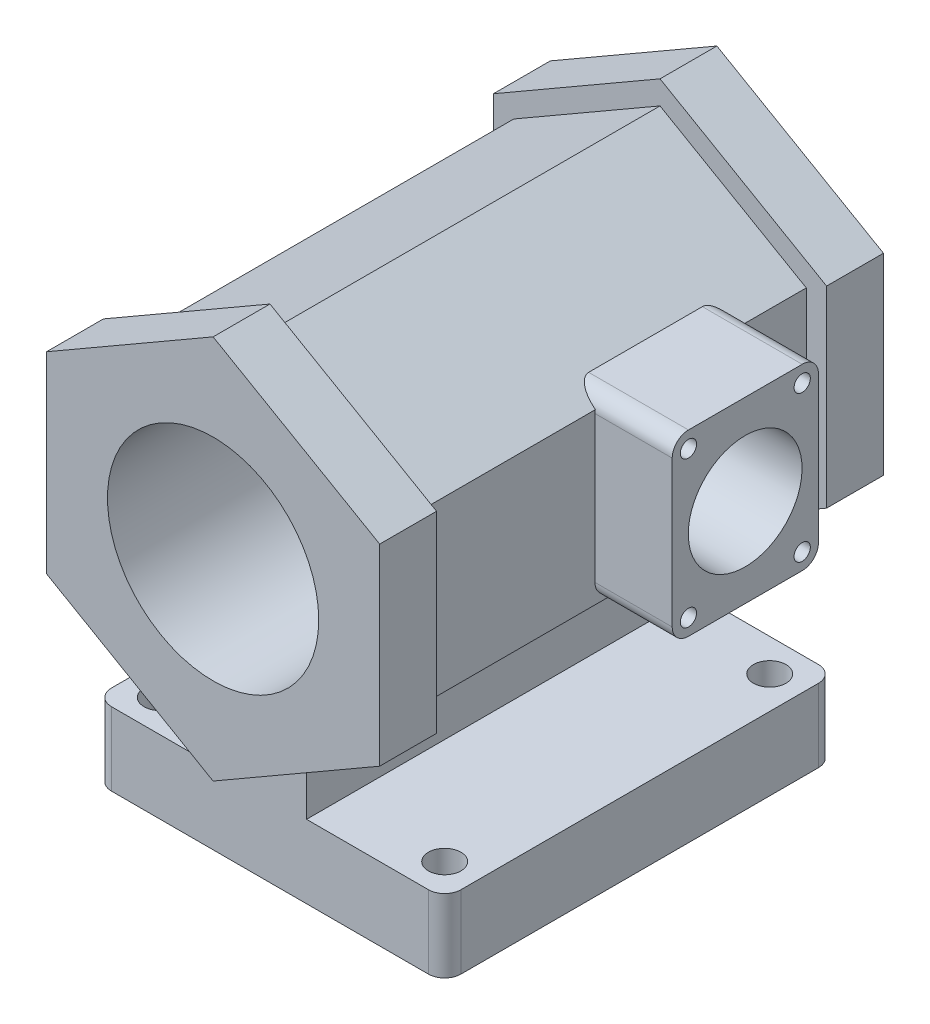
SolidWorks part; units mm, degrees
ref_plane "Спереди" through (0, 0, 0) normal (0, 0, 1) x (1, 0, 0)
ref_plane "Сверху" through (0, 0, 0) normal (0, 1, 0) x (1, 0, 0)
ref_plane "Справа" through (0, 0, 0) normal (1, 0, 0) x (0, 0, -1)
sketch "Эскиз1" plane through (0, 0, 0) normal (0, 0, 1) x (1, 0, 0)
  line L0 (0, 103.923) -> (0, -600.6871) construction
  line L1 (0, 103.923) -> (-90, 51.9615)
  line L2 (-90, 51.9615) -> (-90, -51.9615)
  line L3 (-90, -51.9615) -> (-22.5, -90.9327)
  line L4 (22.5, -90.9327) -> (90, -51.9615)
  line L5 (90, -51.9615) -> (90, 51.9615)
  line L6 (90, 51.9615) -> (0, 103.923)
  line L7 (0, 0) -> (0, -190)
  line L8 (107.5, -190) -> (-107.5, -190)
  line L9 (-107.5, -190) -> (-107.5, -145)
  line L10 (-107.5, -145) -> (-22.5, -145)
  line L11 (-22.5, -145) -> (-22.5, -90.9327)
  line L12 (107.5, -190) -> (107.5, -145)
  line L13 (107.5, -145) -> (22.5, -145)
  line L14 (22.5, -145) -> (22.5, -90.9327)
  circle A0 centre (0, 0) radius 90 construction
  dimension "D1" = 180
  dimension "D2" = 190
  dimension "D3" = 107.5
  dimension "D4" = 45
  dimension "D5" = 85
  dimension "D6" = 215
  dimension "D7" = 45
extrude "Бобышка-Вытянуть1" add sketch "Эскиз1" along normal blind 240 contours L2 L3 L11 L10 L9 L8 L12 L13 L14 L4 L5 L6 L1
sketch "Эскиз2" plane through (0, 0, 240) normal (0, 0, 1) x (1, 0, 0)
  line L1 (0, 118.3568) -> (-102.5, 59.1784)
  line L2 (-102.5, 59.1784) -> (-102.5, -59.1784)
  line L3 (-102.5, -59.1784) -> (0, -118.3568)
  line L4 (0, -118.3568) -> (102.5, -59.1784)
  line L5 (102.5, -59.1784) -> (102.5, 59.1784)
  line L6 (102.5, 59.1784) -> (0, 118.3568)
  circle A0 centre (0, 0) radius 102.5 construction
  dimension "D1" = 205
extrude "Бобышка-Вытянуть2" add sketch "Эскиз2" along normal blind 35
sketch "Эскиз6" plane through (0, 0, 0) normal (0, 0, -1) x (-1, 0, 0)
  line L1 (0, 118.3568) -> (-102.5, 59.1784)
  line L2 (-102.5, 59.1784) -> (-102.5, -59.1784)
  line L3 (-102.5, -59.1784) -> (0, -118.3568)
  line L4 (0, -118.3568) -> (102.5, -59.1784)
  line L5 (102.5, -59.1784) -> (102.5, 59.1784)
  line L6 (102.5, 59.1784) -> (0, 118.3568)
  circle A0 centre (0, 0) radius 102.5 construction
  dimension "D1" = 205
extrude "Бобышка-Вытянуть3" add sketch "Эскиз6" along normal blind 35
sketch "Эскиз9" plane through (102.5, 0, 0) normal (1, 0, 0) x (0, 0, -1)
  line L2 (-240, -190) -> (0, -190) construction
  line L4 (-130, -50) -> (-40, -50)
  line L5 (-130, -50) -> (-130, 60)
  line L6 (-130, 60) -> (-40, 60)
  line L7 (-40, -50) -> (-40, 60)
  line L8 (-130, -50) -> (-40, 60) construction
  line L9 (-130, 60) -> (-40, -50) construction
  point P0 (-2.174, 0)
  point P1 (-85, 5)
  point P4 (-85, 5)
  dimension "D1" = 85
  dimension "D2" = 195
  dimension "D3" = 90
  dimension "D4" = 110
extrude "Бобышка-Вытянуть5" add sketch "Эскиз9" along normal blind 35 and the other way blind 90
sketch "Эскиз10" plane through (0, 0, 275) normal (0, 0, 1) x (1, 0, 0)
  circle A0 centre (0, 0) radius 65
  dimension "D1" = 130
extrude "Вырез-Вытянуть1" cut sketch "Эскиз10" against normal through all
sketch "Эскиз12" plane through (137.5, 0, 0) normal (1, 0, 0) x (0, 0, -1)
  circle A0 centre (-85.1023, 4.5747) radius 35
  dimension "D1" = 70
extrude "Вырез-Вытянуть2" cut sketch "Эскиз12" against normal up to next
sketch "Эскиз15" plane through (0, -190, 0) normal (0, -1, 0) x (-1, 0, 0)
  line L0 (-107.5, -240) -> (107.5, -240) construction
  line L1 (107.5, -240) -> (107.5, 0) construction
  line L2 (-107.5, -240) -> (-107.5, 0) construction
  line L3 (-107.5, 0) -> (107.5, 0) construction
  circle A0 centre (87.5, -220) radius 10
  circle A1 centre (-87.5, -220) radius 10
  circle A2 centre (-87.5, -20) radius 10
  circle A3 centre (87.5, -20) radius 10
  point P0 (87.5, -220)
  point P8 (-87.5, -220)
  point P12 (-87.5, -20)
  point P13 (-87.5, -20)
  point P18 (87.5, -20)
  dimension "D3" = 20
  dimension "D6" = 20
  dimension "D9" = 20
  dimension "D12" = 20
  dimension "D1" = 20
  dimension "D2" = 20
  dimension "D4" = 20
  dimension "D5" = 20
  dimension "D7" = 20
  dimension "D8" = 20
  dimension "D10" = 20
  dimension "D11" = 20
extrude "Вырез-Вытянуть3" cut sketch "Эскиз15" against normal up to next
sketch "Эскиз16" plane through (137.5, 0, 0) normal (1, 0, 0) x (0, 0, -1)
  line L0 (-130, 60) -> (-40, 60) construction
  line L1 (-130, -50) -> (-130, 51.9615) construction
  line L2 (-40, -50) -> (-40, 60) construction
  line L3 (-40, 60) -> (-130, 60) construction
  line L4 (-130, -50) -> (-40, -50) construction
  line L5 (-130, 60) -> (-130, -50) construction
  line L6 (-40, 51.9615) -> (-40, -50) construction
  circle A0 centre (-120, 50) radius 5
  circle A1 centre (-50, 50) radius 5
  circle A2 centre (-120, -40) radius 5
  circle A3 centre (-50, -40) radius 5
  point P0 (-120, 50)
  point P8 (-50, 50)
  point P16 (-120, -40)
  point P24 (-50, -40)
  dimension "D3" = 10
  dimension "D6" = 10
  dimension "D9" = 10
  dimension "D12" = 10
  dimension "D1" = 10
  dimension "D2" = 10
  dimension "D4" = 10
  dimension "D5" = 10
  dimension "D7" = 10
  dimension "D8" = 10
  dimension "D10" = 10
  dimension "D11" = 10
extrude "Вырез-Вытянуть4" cut sketch "Эскиз16" against normal blind 30
fillet "Скругление13" radius 10 4 edges at (106.7885, 60, 40) (106.7885, 60, 130) (113.75, -50, 40) (113.75, -50, 130)
fillet "Скругление15" radius 10 4 edges at (107.5, -167.5, 0) (107.5, -167.5, 240) (-107.5, -167.5, 240) (-107.5, -167.5, 0)
